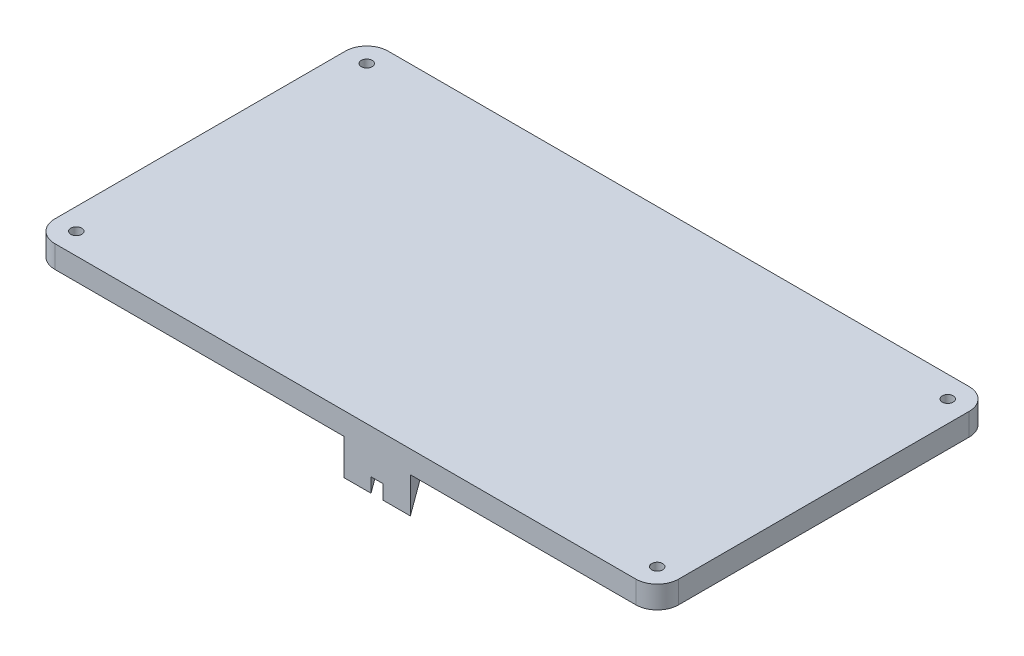
SolidWorks part; units mm, degrees
ref_plane "前视基准面" through (0, 0, 0) normal (0, 0, 1) x (1, 0, 0)
ref_plane "上视基准面" through (0, 0, 0) normal (0, 1, 0) x (1, 0, 0)
ref_plane "右视基准面" through (0, 0, 0) normal (1, 0, 0) x (0, 0, -1)
sketch "草图2" plane through (0, 0, 0) normal (0, 1, 0) x (1, 0, 0)
  line L0 (-65, -71.4285) -> (65, -71.4285) construction
  line L1 (31.2175, -10.8468) -> (46.7825, -58.3625) construction
  line L2 (35.9691, -9.2904) -> (51.534, -56.806) construction
  line L3 (35.9691, -9.2904) -> (29.602, -11.3761) construction
  line L4 (29.602, -11.3761) -> (45.1669, -58.8917) construction
  line L5 (51.534, -56.806) -> (45.1669, -58.8917) construction
  line L6 (0, -137.5901) -> (0, 34.855) construction
  line L7 (-5.9166, -55.1649) -> (5.9166, -71.2887) construction
  line L8 (5.9166, -71.2887) -> (7.529, -70.1053) construction
  line L9 (7.529, -70.1053) -> (-4.3042, -53.9816) construction
  line L10 (-4.3042, -53.9816) -> (-5.9166, -55.1649) construction
  line L11 (120.7724, 25.4082) -> (-26.0498, -82.3448) construction
  line L12 (181.8624, 12.1935) -> (-42.886, -61.4285) construction
  line L13 (-93.8575, -34.6046) -> (197.9515, -34.6046) construction
  line L14 (-71, -24.6046) -> (-71, -44.6046)
  line L15 (-70, -1.4285) -> (-70, -66.4285) construction
  line L16 (-65, 3.5715) -> (65, 3.5715) construction
  line L17 (70, -1.4285) -> (70, -66.4285) construction
  line L22 (-3.2316, -46.9924) -> (-10.3584, -52.2227)
  line L23 (-10.3584, -57.5635) -> (-0.1828, -71.4285)
  line L25 (14.5182, -71.178) -> (-3.2316, -46.9924)
  line L26 (-4.2828, -53.8418) -> (-6.0564, -55.1435)
  line L27 (-6.0564, -55.1435) -> (5.8952, -71.4285)
  line L29 (7.6688, -70.1268) -> (-4.2828, -53.8418)
  line L30 (-12.9059, -54.0923) -> (4.844, -78.2779) construction
  line L31 (4.844, -78.2779) -> (14.5182, -71.178) construction
  line L32 (14.5182, -71.178) -> (14.7021, -71.4285)
  line L33 (39.1642, -2.9823) -> (23.294, -8.181)
  line L34 (23.294, -8.181) -> (41.9719, -65.1997)
  line L35 (57.8421, -60.001) -> (41.9719, -65.1997)
  line L36 (39.1642, -2.9823) -> (57.8421, -60.001)
  line L37 (36.033, -9.1642) -> (29.4758, -11.3122)
  line L38 (29.4758, -11.3122) -> (45.103, -59.0178)
  line L39 (51.6602, -56.8699) -> (45.103, -59.0178)
  line L40 (36.033, -9.1642) -> (51.6602, -56.8699)
  line L42 (-17.9883, -76.4285) -> (0, -76.4285)
  line L45 (-71, -24.6046) -> (-70, -24.6046)
  line L46 (-71, -44.6046) -> (-70, -44.6046)
  line L47 (-71, -34.6046) -> (48.9552, -59.6837) construction
  line L48 (-71, -34.6046) -> (25.7263, -62.7063) construction
  line L49 (-10.3584, -52.2227) -> (-10.3584, -71.4285)
  line L50 (-3.2316, -46.9924) -> (-12.9059, -54.0923) construction
  line L51 (-10.3584, -52.2227) -> (-15.3584, -50.7701)
  line L52 (-15.3584, -50.7701) -> (-15.3584, -71.4285)
  line L53 (7.6688, -70.1268) -> (8.6241, -71.4285)
  line L54 (69.8, -1.4285) -> (69.8, -66.4285)
  line L55 (5.8952, -71.4285) -> (7.6688, -70.1268) construction
  line L56 (-65, -71.2285) -> (65, -71.2285)
  line L57 (-69.8, -1.4285) -> (-69.8, -66.4285)
  line L58 (-65, 3.3715) -> (65, 3.3715)
  arc A0 (-65, -71.4285) -> (-70, -66.4285) centre (-65, -66.4285) cw construction
  arc A1 (65, -71.4285) -> (70, -66.4285) centre (65, -66.4285) ccw construction
  arc A2 (65, 3.5715) -> (70, -1.4285) centre (65, -1.4285) cw construction
  arc A3 (-70, -1.4285) -> (-65, 3.5715) centre (-65, -1.4285) cw construction
  arc A12 (65, -71.2285) -> (69.8, -66.4285) centre (65, -66.4285) ccw
  arc A13 (-65, -71.2285) -> (-69.8, -66.4285) centre (-65, -66.4285) cw
  arc A14 (-69.8, -1.4285) -> (-65, 3.3715) centre (-65, -1.4285) cw
  arc A15 (65, 3.3715) -> (69.8, -1.4285) centre (65, -1.4285) cw
  circle A16 centre (-65, -1.4285) radius 1.225
  circle A17 centre (-65, -66.4285) radius 1.225
  circle A18 centre (65, -66.4285) radius 1.225
  circle A19 centre (65, -1.4285) radius 1.225
  point P10 (0, -71.4285)
  point P14 (0, -63.2268)
  point P21 (39, -34.6046)
  point P29 (-71, -34.6046)
  point P118 (-70, -34.6046)
  dimension "D13" = 5
  dimension "D14" = 5
  dimension "D25" = 2.45
  dimension "D2" = 6.7
  dimension "D3" = 50
  dimension "D4" = 5
  dimension "D5" = 20
  dimension "D6" = 2
  dimension "D7" = 53.725
  dimension "D8" = 18.138
  dimension "D9" = 110
  dimension "D10" = 1
  dimension "D11" = 20
  dimension "D12" = 140
  dimension "D21" = 5
  dimension "D26" = 38.1762
  dimension "D15" = 0.2
  dimension "D16" = 5
  dimension "D17" = 0.1
  dimension "D18" = 5
  dimension "D19" = 0.1
extrude "凸台-拉伸1" add sketch "草图2" against normal blind 5 contours L58 A15 L54 A12 L56 A13 L57 A14
extrude "凸台-拉伸2" add sketch "草图2<19>" against normal blind 13 contours L29 L53 L32 L25 L22 L49 L23 L27 L26 region at (5.3631, 0, 59.2908)
sketch "草图2<19>" plane through (0, 0, 0) normal (0, 1, 0) x (1, 0, 0) same geometry as "草图2"
extrude "凸台-拉伸3" add sketch "草图2<20>" against normal blind 10 contours L36 L33 L34 L35 L37 L40 L39 L38 region at (47.8268, 0, 31.7132)
sketch "草图2<20>" plane through (0, 0, 0) normal (0, 1, 0) x (1, 0, 0) same geometry as "草图2"
extrude "凸台-拉伸4" add sketch "草图2<21>" against normal blind 7.28 contours L40 L37 L38 L39 region at (40.568, 0, 34.091)
sketch "草图2<21>" plane through (0, 0, 0) normal (0, 1, 0) x (1, 0, 0) same geometry as "草图2"
extrude "凸台-拉伸5" add sketch "草图2<22>" against normal blind 9.8 contours L53 L29 L26 L27 L0 region at (0.9862, 0, 62.8563)
sketch "草图2<22>" plane through (0, 0, 0) normal (0, 1, 0) x (1, 0, 0) same geometry as "草图2"
extrude "切除-拉伸1" cut sketch "草图2<23>" against normal blind 5 contours A16 | A17 | A19 | A18
sketch "草图2<23>" plane through (0, 0, 0) normal (0, 1, 0) x (1, 0, 0) same geometry as "草图2"
